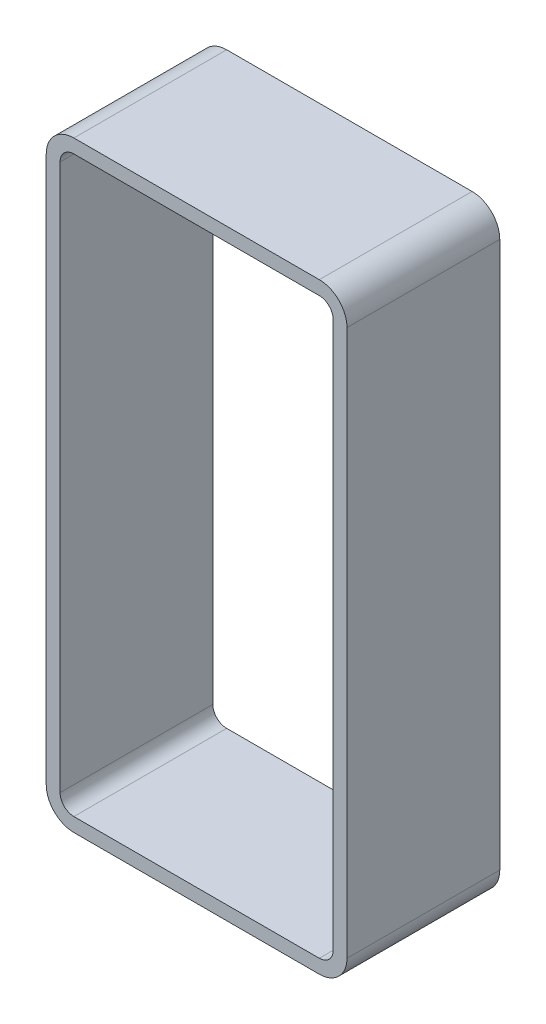
SolidWorks part; units mm, degrees
ref_plane "Front Plane" through (0, 0, 0) normal (0, 0, 1) x (1, 0, 0)
ref_plane "Top Plane" through (0, 0, 0) normal (0, 1, 0) x (1, 0, 0)
ref_plane "Right Plane" through (0, 0, 0) normal (1, 0, 0) x (0, 0, -1)
sketch "Sketch1" plane through (0, 0, 0) normal (0, 0, 1) x (1, 0, 0)
  line L0 (-20.4, 47.7) -> (20.4, 47.7)
  line L1 (-20.4, -50) -> (20.4, -50)
  line L2 (-25, -45.4) -> (-25, 45.4)
  line L3 (-20.4, 50) -> (20.4, 50)
  line L4 (25, -45.4) -> (25, 45.4)
  line L5 (-25, -50) -> (25, 50) construction
  line L6 (-25, 50) -> (25, -50) construction
  line L7 (22.7, -45.4) -> (22.7, 45.4)
  line L8 (-20.4, -47.7) -> (20.4, -47.7)
  line L9 (-22.7, -45.4) -> (-22.7, 45.4)
  arc A0 (-25, 45.4) -> (-20.4, 50) centre (-20.4, 45.4) cw
  arc A1 (20.4, 50) -> (25, 45.4) centre (20.4, 45.4) cw
  arc A2 (-20.4, -50) -> (-25, -45.4) centre (-20.4, -45.4) cw
  arc A3 (20.4, -50) -> (25, -45.4) centre (20.4, -45.4) ccw
  arc A4 (-22.7, 45.4) -> (-20.4, 47.7) centre (-20.4, 45.4) cw
  arc A5 (20.4, 47.7) -> (22.7, 45.4) centre (20.4, 45.4) cw
  arc A6 (20.4, -47.7) -> (22.7, -45.4) centre (20.4, -45.4) ccw
  arc A7 (-20.4, -47.7) -> (-22.7, -45.4) centre (-20.4, -45.4) cw
  point P0 (0, 0)
  dimension "D2" = 4.6
  dimension "Thickness" = 2.3
extrude "BaseSection" add sketch "Sketch1" along normal mid plane 25.4
equation "\"D2@Sketch1\" = \"Thickness@Sketch1\" * (  (IIf(\"Thickness@Sketch1\">3, 1.5, 1))  + 1 ) "
